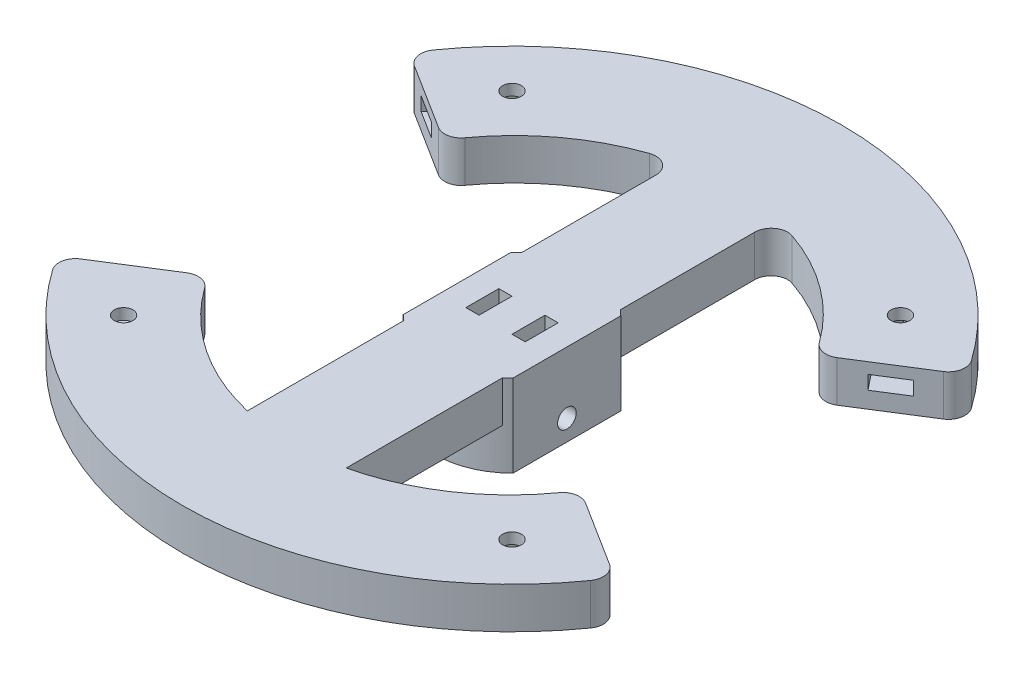
SolidWorks part; units mm, degrees
ref_plane "Front Plane" through (0, 0, 0) normal (0, 0, 1) x (1, 0, 0)
ref_plane "Top Plane" through (0, 0, 0) normal (0, 1, 0) x (1, 0, 0)
ref_plane "Right Plane" through (0, 0, 0) normal (1, 0, 0) x (0, 0, -1)
sketch "Sketch1" plane through (0, 0, 0) normal (0, 1, 0) x (1, 0, 0)
  line L0 (0, 0) -> (0, 6.5587) construction
  line L1 (-10, 9.798) -> (-10, -9.798)
  line L2 (10, 9.798) -> (10, -9.798)
  line L5 (0, 0) -> (0, -5.5176) construction
  arc A0 (-10, -9.798) -> (10, -9.798) centre (0, 0) ccw
  arc A1 (-10, 9.798) -> (10, 9.798) centre (0, 0) cw
  dimension "D1" = 14
  dimension "D2" = 20
extrude "Boss-Extrude1" add sketch "Sketch1" along normal blind 15
ref_plane "Plane1" through (3, 0, 0) normal (1, 0, 0) x (0, 0, -1)
sketch "Sketch2" plane through (3, 0, 0) normal (1, 0, 0) x (0, 0, -1)
  line L0 (0, 0) -> (0, 15) construction
  line L2 (14, 15) -> (10.7238, 15) construction
  line L4 (0, 0.3) -> (3, 2.0321)
  line L5 (3, 2.0321) -> (3, 5.4962)
  line L8 (-3, 5.4962) -> (-3, 2.0321)
  line L9 (-3, 2.0321) -> (0, 0.3)
  line L10 (10.7238, 0) -> (14, 0) construction
  line L11 (-3, 5.4962) -> (-3, 15)
  line L12 (3, 5.4962) -> (3, 15)
  line L13 (3, 15) -> (-3, 15)
  line L23 (0, 7.2282) -> (-1.5, 6.3622)
  line L24 (1.5, 6.3622) -> (0, 7.2282)
  circle A0 centre (0, 3.7641) radius 3 construction
  dimension "D1" = 6
  dimension "D2" = 0.3
extrude "Cut-Extrude1" cut sketch "Sketch2" along normal blind 2.4
sketch "Sketch4" plane through (0, 0, 0) normal (0, -1, 0) x (1, 0, 0)
  line L2 (-1.5, 0) -> (-1.5, -2) construction
  line L4 (-1.5, -2) -> (-1.5, 2)
  line L5 (1.5, -2) -> (1.5, 2)
  arc A0 (-1.5, -2) -> (1.5, -2) centre (0, 0) ccw
  arc A1 (1.5, 2) -> (-1.5, 2) centre (0, 0) ccw
  dimension "D1" = 5
  dimension "D2" = 3
extrude "Cut-Extrude3" cut sketch "Sketch4" against normal blind 8
sketch "Sketch5" plane through (0, 0, 0) normal (1, 0, 0) x (0, 0, -1)
  line L0 (0, 0) -> (0, 7.52) construction
  circle A0 centre (0, 3.76) radius 1.7
  dimension "D1" = 3.4
  dimension "D2" = 3.76
extrude "Cut-Extrude4" cut sketch "Sketch5" against normal through all both and the other way through all
mirror "Mirror1" about plane through (0, 0, 0) normal (1, 0, 0) of "Cut-Extrude1"
sketch "Sketch7" plane through (0, 15, 0) normal (0, 1, 0) x (1, 0, 0)
  line L0 (-9, 10.7238) -> (-9, 39.1723)
  line L1 (-13.0667, 0) -> (-35.2977, 0) construction
  line L2 (-13.0667, 5.0262) -> (-13.0667, -5.0262) construction
  line L3 (0, 0) -> (0, 14) construction
  line L4 (9, 10.7238) -> (9, 39.1723)
  line L5 (-9, 10.7238) -> (9, 10.7238)
  line L6 (9, -10.7238) -> (9, -39.1723)
  line L7 (-9, -10.7238) -> (9, -10.7238)
  line L8 (-9, -10.7238) -> (-9, -39.1723)
  line L9 (0, 0) -> (0, 50) construction
  line L10 (0, 0) -> (-53.635, -53.635) construction
  line L11 (0, 0) -> (-53.635, 53.635) construction
  line L12 (0, 0) -> (53.635, 53.635) construction
  line L13 (0, 0) -> (53.635, -53.635) construction
  line L14 (-9, 14) -> (-75.9677, 14) construction
  line L15 (0, -14) -> (-85.9074, -14) construction
  line L16 (50.7365, 32.0283) -> (33.8243, 21.3522)
  line L18 (-50.7365, -32.0283) -> (-33.8243, -21.3522)
  line L19 (50.7365, -32.0283) -> (33.8243, -21.3522)
  line L20 (0, 0) -> (-73.9481, 46.6811) construction
  line L21 (-50.7365, 32.0283) -> (-33.8243, 21.3522)
  arc A0 (9, 10.7238) -> (-9, 10.7238) centre (0, 0) ccw construction
  arc A1 (-33.8243, 21.3522) -> (-9, 39.1723) centre (0, 0.4341) cw
  circle A2 centre (35.3553, 35.3553) radius 1.7
  circle A3 centre (0, 0) radius 50 construction
  arc A4 (-50.7365, -32.0283) -> (50.7365, -32.0283) centre (0, 0) ccw
  arc A5 (-33.8243, -21.3522) -> (-9, -39.1723) centre (0, -0.4341) ccw
  circle A6 centre (-35.3553, 35.3553) radius 1.7
  arc A7 (9, 39.1723) -> (33.8243, 21.3522) centre (0, 0.4341) cw
  circle A8 centre (35.3553, -35.3553) radius 1.7
  circle A9 centre (-35.3553, -35.3553) radius 1.7
  arc A10 (-9, -10.7238) -> (9, -10.7238) centre (0, 0) ccw construction
  arc A11 (9, -39.1723) -> (33.8243, -21.3522) centre (0, -0.4341) ccw
  circle A12 centre (0, 0) radius 60 construction
  arc A14 (50.7365, 32.0283) -> (-50.7365, 32.0283) centre (0, 0) ccw
  point P14 (40, 0)
  point P25 (0, 0)
  point P34 (0, 0)
  point P42 (0, 0)
  point P50 (60, 0)
  dimension "D4" = 10
  dimension "D8" = 3.4
  dimension "D1" = 4
  dimension "D3" = 50
  dimension "D6" = 135
  dimension "D7" = 4
extrude "Boss-Extrude2" add sketch "Sketch7" against normal blind 7.5
sketch "Sketch17" plane through (0, 0, 0) normal (0, -1, 0) x (1, 0, 0)
  circle A0 centre (0, 0) radius 2.5
  dimension "D1" = 5
extrude "Cut-Extrude5" cut sketch "Sketch17" against normal blind 1
ref_plane "Plane2" through (0, 13, 0) normal (0, 1, 0) x (1, 0, 0)
sketch "Sketch18" plane through (0, 13, 0) normal (0, 1, 0) x (1, 0, 0)
  line L0 (-35.3553, 35.3553) -> (-42.2804, 26.6902) construction
  line L1 (-50.7365, 32.0283) -> (-33.8243, 21.3522) construction
  line L2 (-38.7802, 35.8752) -> (-44.833, 28.3016)
  line L4 (-34.0931, 32.1294) -> (-31.9305, 34.8355)
  line L5 (-31.9305, 34.8355) -> (-33.1927, 38.0614)
  line L6 (-33.1927, 38.0614) -> (-36.6175, 38.5813)
  line L7 (-36.6175, 38.5813) -> (-38.7802, 35.8752)
  line L9 (-34.0931, 32.1294) -> (-39.7278, 25.0789)
  line L10 (-39.7278, 25.0789) -> (-44.833, 28.3016)
  line L12 (-38.1491, 34.2622) -> (-37.518, 32.6493)
  line L13 (-35.8056, 32.3893) -> (-34.0931, 32.1294)
  circle A0 centre (-35.3553, 35.3553) radius 3 construction
  dimension "D1" = 6
extrude "Cut-Extrude6" cut sketch "Sketch18" against normal blind 2.5
mirror "Mirror2" about plane through (0, 0, 0) normal (1, 0, 0) of "Cut-Extrude6"
mirror "Mirror3" about plane through (0, 0, 0) normal (0, 0, 1) of "Mirror2", "Cut-Extrude6"
fillet "Fillet1" radius 3 10 edges at (-50.7365, 11.25, 32.0283) (-33.8243, 11.25, 21.3522) (-50.7365, 11.25, -32.0283) (-33.8243, 11.25, -21.3522) (-9, 11.25, -39.1723) (50.7365, 11.25, 32.0283) (33.8243, 11.25, 21.3522) (50.7365, 11.25, -32.0283) (33.8243, 11.25, -21.3522) (9, 11.25, -39.1723)
